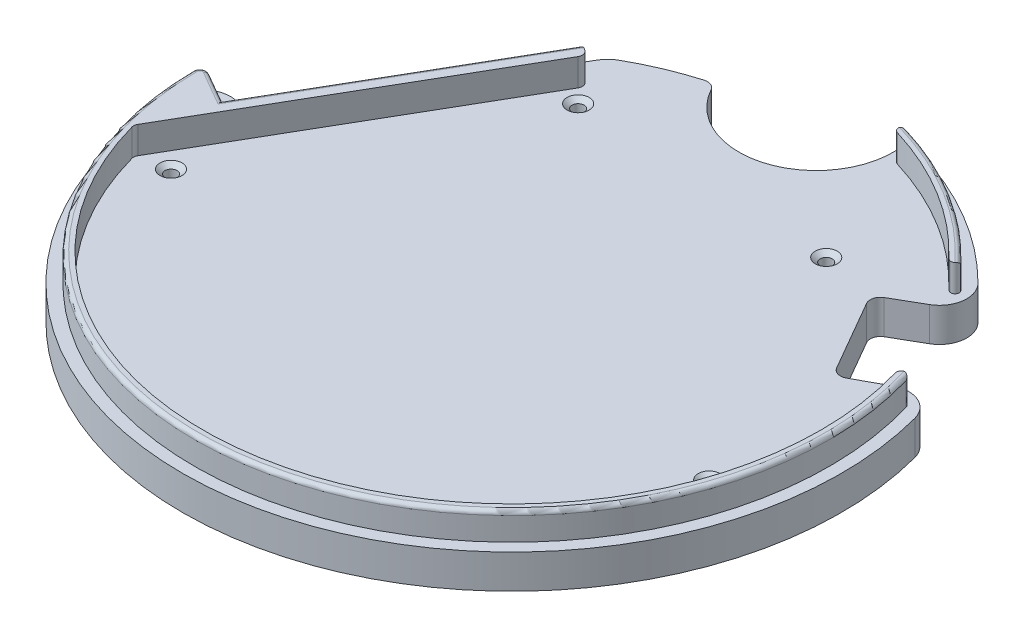
SolidWorks part; units mm, degrees
ref_plane "Front Plane" through (0, 0, 0) normal (0, 0, 1) x (1, 0, 0)
ref_plane "Top Plane" through (0, 0, 0) normal (0, 1, 0) x (1, 0, 0)
ref_plane "Right Plane" through (0, 0, 0) normal (1, 0, 0) x (0, 0, -1)
sketch "Sketch1" plane through (0, 0, 0) normal (0, 1, 0) x (1, 0, 0)
  line L0 (0, 0) -> (0, -80.4493) construction
  line L1 (0, 0) -> (82.8336, 47.824) construction
  line L2 (0, 0) -> (-93.2103, 53.815) construction
  line L3 (0, 0) -> (0, 41.0443) construction
  line L4 (-40.2546, 23.241) -> (-52.3516, 2.2884)
  line L5 (-52.3516, 2.2884) -> (-32.2536, 37.0991)
  line L8 (35.4921, 31.4899) -> (45.0171, 14.9921)
  line L9 (35.4921, 31.4899) -> (47.9387, 38.6759)
  line L10 (45.0171, 14.9921) -> (57.593, 21.84)
  line L16 (-52.3516, 2.2884) -> (-61.1525, 7.3697)
  line L17 (0.033, 41.0443) -> (0, 41.0443)
  line L19 (0, 56.8616) -> (0, 82.8872) construction
  line L20 (-32.2536, 37.0991) -> (-27.3746, 45.3039)
  arc A2 (47.9387, 38.6759) -> (14.1319, 59.9519) centre (0, 0) ccw
  arc A5 (-13.3237, 51.2279) -> (14.1319, 59.9519) centre (0, 56.8616) ccw
  arc A6 (-61.1525, 7.3697) -> (57.593, 21.84) centre (0, 0) ccw
  arc A7 (-13.3237, 51.2279) -> (-27.3746, 45.3039) centre (0, 0) ccw
  dimension "D1" = 120
  dimension "D6" = 61.595
  dimension "D7" = 61.595
  dimension "D2" = 120
  dimension "D3" = 60
  dimension "D4" = 46.482
  dimension "D5" = 16.002
  dimension "D8" = 9.525
  dimension "D9" = 9.525
extrude "Boss-Extrude1" add sketch "Sketch1" along normal blind 6.35 contours L5 L4 L10 L8 L9 A2 region at (2.0366, 0, 5.6186)
sketch "Sketch9" plane through (0, 0, 0) normal (0, 1, 0) x (1, 0, 0)
  line L0 (0, 0) -> (0, 65.1474) construction
  line L1 (0, 0) -> (75.6303, 43.6651) construction
  line L2 (0, 0) -> (-69.9813, 40.4037) construction
  line L3 (0, 0) -> (-22.8258, 35.1487) construction
  line L4 (0, 0) -> (25.2221, 33.4708) construction
  line L5 (0, 0) -> (-50.2958, -13.4767) construction
  line L6 (0, 0) -> (50.2958, -13.4767) construction
  point P10 (-22.8258, 35.1487)
  point P11 (-50.2958, -13.4767)
  point P12 (25.2221, 33.4708)
  point P13 (50.2958, -13.4767)
  point P14 (-50.2958, -13.4767)
  point P15 (-22.8258, 35.1487)
  point P16 (25.2221, 33.4708)
  point P17 (50.2958, -13.4767)
  dimension "D2" = 52.07
  dimension "D3" = 41.91
  dimension "D4" = 41.91
  dimension "D5" = 33
  dimension "D6" = 37
  dimension "D7" = 52.07
  dimension "D8" = 60
  dimension "D9" = 60
  dimension "D10" = 45
  dimension "D12" = 45
sketch "Sketch11" plane through (0, 6.35, 0) normal (0, 1, 0) x (1, 0, 0)
  line L0 (-51.6425, -2.5204) -> (-59.3159, 1.9099)
  line L2 (55.183, 17.0571) -> (56.6045, 17.8312)
  line L3 (45.0171, 14.9921) -> (57.593, 21.84) construction
  line L4 (42.5348, 39.0755) -> (43.9426, 39.8883)
  line L5 (35.4921, 31.4899) -> (47.9387, 38.6759) construction
  line L7 (-26.9682, 40.1129) -> (-51.6425, -2.5204)
  line L8 (-24.7699, 38.8406) -> (-55.8257, -14.819)
  line L10 (-26.9682, 40.1129) -> (-24.7699, 38.8406)
  line L11 (-52.3516, 2.2884) -> (-61.1525, 7.3697) construction
  line L12 (15.6499, 55.5985) -> (16.08, 57.1267)
  arc A1 (-59.3159, 1.9099) -> (56.6045, 17.8312) centre (0, 0) ccw
  arc A3 (-55.8257, -14.819) -> (55.183, 17.0571) centre (0, 0) ccw
  arc A4 (43.9426, 39.8883) -> (16.08, 57.1267) centre (0, 0) ccw
  arc A5 (42.5348, 39.0755) -> (15.6499, 55.5985) centre (0, 0) ccw
  dimension "D1" = 3.81
  dimension "D2" = 2.54
  dimension "D3" = 3.048
  dimension "D5" = 59.3466
  dimension "D6" = 57.7591
  dimension "D4" = 3.048
  dimension "D7" = 40.894
extrude "Boss-Extrude6" add sketch "Sketch11" along normal blind 5.08
fillet "Fillet14" radius 5.08 4 edges at (47.9387, 3.175, -38.6759) (-61.1525, 3.175, -7.3697) (57.593, 3.175, -21.84) (-27.3746, 3.175, -45.3039)
fillet "Fillet16" radius 1.905 6 edges at (45.0171, 3.175, -14.9921) (35.4921, 3.175, -31.4899) (-13.3237, 3.175, -51.2279) (14.1319, 3.175, -59.9519) (-32.2536, 3.175, -37.0991) (-52.3516, 3.175, -2.2884)
fillet "Fillet17" radius 1.27 6 edges at (-59.3159, 8.89, -1.9099) (42.5348, 8.89, -39.0755) (55.183, 8.89, -17.0571) (-24.7699, 8.89, -38.8406) (-55.8257, 8.89, 14.819) (15.6499, 8.89, -55.5985)
fillet "Fillet18" radius 0.762 9 edges at (56.6045, 8.89, -17.8312) (43.9426, 8.89, -39.8883) (-26.9682, 8.89, -40.1129) (16.08, 8.89, -57.1267) (-54.5417, 11.43, 0.8465) (-58.7136, 11.43, -0.8259) (-39.3054, 11.43, -18.7963) (31.2245, 11.43, -50.4684) (9.1579, 11.43, 58.6358)
hole_wizard "#4-40 Tapped Hole2" positions "Sketch19" profile "Sketch20" tap size "#4-40" standard "ANSI Inch" end condition through all
sketch "Sketch19" plane through (0, 6.35, 0) normal (0, 1, 0) x (1, 0, 0)
  point P4 (-22.8308, 35.1967)
  point P6 (-50.2769, -13.4385)
  point P8 (50.3076, -13.4385)
  point P10 (25.237, 33.5059)
sketch "Sketch20" plane through (-22.8308, 6.35, -35.1967) normal (1, 0, 0) x (0, 0, 1)
  line L0 (0, 0) -> (0, 6.35)
  line L1 (0, 6.35) -> (1.1303, 6.35)
  line L2 (1.1303, 6.35) -> (1.1303, 0.7779)
  line L3 (1.1303, 0.7779) -> (2.0574, 0)
  line L5 (2.0574, 0) -> (0, 0)
  line L6 (-1.1303, 0.7779) -> (-2.0574, 0) construction
  line L11 (0, -6.35) -> (0, 107.95) construction
  dimension "Thru Tap Drill Dia." = 2.2606
  dimension "Thru Tap Drill Depth" = 6.35
  dimension "Near C'Sink Dia." = 4.1148
  dimension "Near C'Sink Angle" = 100
cosmetic thread "Hole Thread5" parameters "D2"=2.8448
cosmetic thread "Hole Thread6" parameters "D2"=2.8448
cosmetic thread "Hole Thread7" parameters "D2"=2.8448
cosmetic thread "Hole Thread8" parameters "D2"=2.8448
